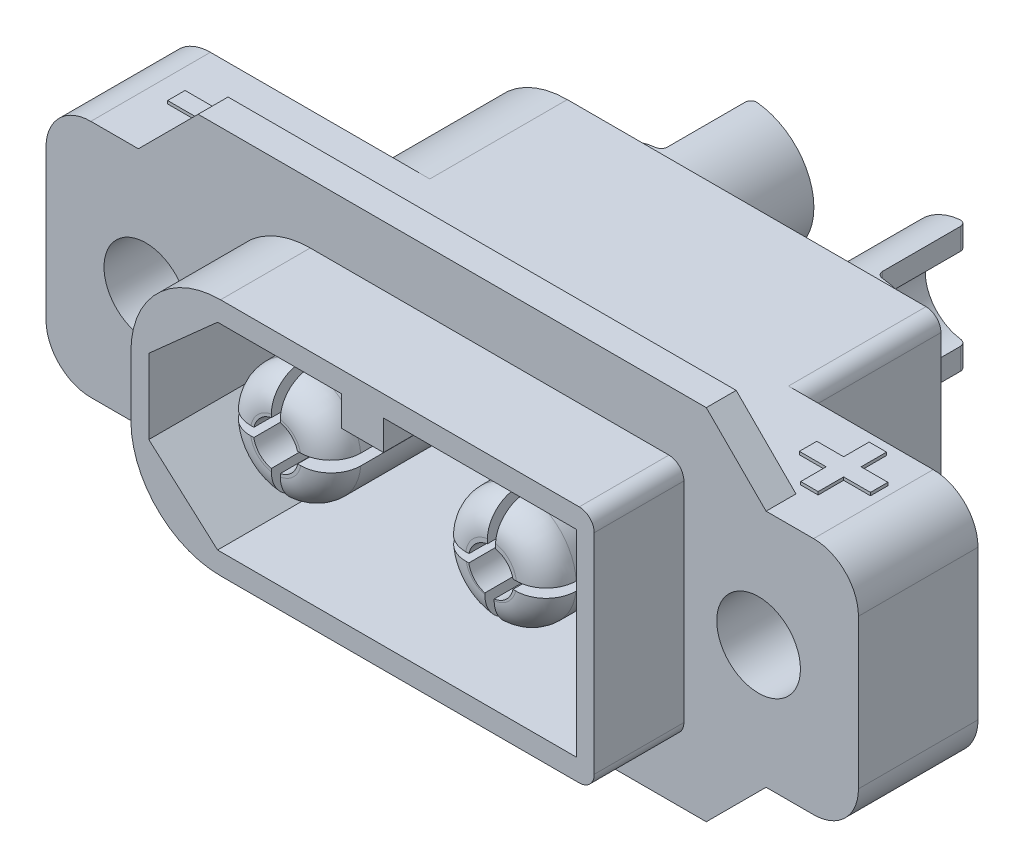
SolidWorks part; units mm, degrees
ref_plane "Front Plane" through (0, 0, 0) normal (0, 0, 1) x (1, 0, 0)
ref_plane "Top Plane" through (0, 0, 0) normal (0, 1, 0) x (1, 0, 0)
ref_plane "Right Plane" through (0, 0, 0) normal (1, 0, 0) x (0, 0, -1)
sketch "Sketch1" plane through (0, 0, 0) normal (0, 0, 1) x (1, 0, 0)
  line L1 (7.75, -4) -> (-7.75, -4)
  line L2 (7.75, -4) -> (7.75, 4)
  line L3 (7.75, 4) -> (-7.75, 4)
  line L4 (-7.75, -4) -> (-7.75, 4)
  line L5 (7.75, -4) -> (-7.75, 4) construction
  line L6 (7.75, 4) -> (-7.75, -4) construction
  point P0 (0, 0)
  dimension "D1" = 15.5
  dimension "D2" = 8
extrude "Boss-Extrude1" add sketch "Sketch1" against normal blind 8.6 and the other way blind 3
fillet "Fillet1" radius 3 2 edges at (-7.75, -4, -2.8) (-7.75, 4, -2.8)
fillet "Fillet2" radius 0.5 2 edges at (7.75, -4, -2.8) (7.75, 4, -2.8)
sketch "Sketch2" plane through (0, 0, 0) normal (0, 0, 1) x (1, 0, 0)
  line L0 (7.25, 4) -> (-4.75, 4) construction
  line L1 (13.59, -4) -> (-13.59, -4)
  line L2 (13.59, -4) -> (13.59, 4)
  line L3 (13.59, 4) -> (-13.59, 4)
  line L4 (-13.59, -4) -> (-13.59, 4)
  line L5 (13.59, -4) -> (-13.59, 4) construction
  line L6 (13.59, 4) -> (-13.59, -4) construction
  point P0 (0, 0)
  dimension "D1" = 0
  dimension "D2" = 27.18
extrude "Boss-Extrude2" add sketch "Sketch2" against normal blind 4
fillet "Fillet3" radius 1.5 4 edges at (-13.59, -4, -2) (13.59, -4, -2) (13.59, 4, -2) (-13.59, 4, -2)
sketch "Sketch3" plane through (0, 0, -8.6) normal (0, 0, -1) x (-1, 0, 0)
  line L8 (-7.05, 3.3) -> (-7.05, -3.3)
  line L9 (-7.05, -3.3) -> (4.75, -3.3)
  line L10 (7.05, -1) -> (7.05, 1)
  line L11 (4.75, 3.3) -> (-7.05, 3.3)
  line L12 (-7.05, 3.3) -> (-7.05, -3.3)
  line L13 (-7.05, -3.3) -> (4.75, -3.3)
  line L14 (7.05, -1) -> (7.05, 1)
  line L15 (4.75, 3.3) -> (-7.05, 3.3)
  arc A8 (4.75, -3.3) -> (7.05, -1) centre (4.75, -1) ccw
  arc A9 (7.05, 1) -> (4.75, 3.3) centre (4.75, 1) ccw
  arc A10 (4.75, -3.3) -> (7.05, -1) centre (4.75, -1) ccw
  arc A11 (7.05, 1) -> (4.75, 3.3) centre (4.75, 1) ccw
  dimension "D1" = 0.7
extrude "Cut-Extrude1" cut sketch "Sketch3" against normal blind 1
sketch "Sketch4" plane through (0, 0, 0) normal (0, 0, 1) x (1, 0, 0)
  line L0 (8.5, 6) -> (10.5, 4)
  line L1 (8.5, -6) -> (-8.5, -6)
  line L3 (8.5, 6) -> (-8.5, 6)
  line L5 (8.5, -6) -> (-8.5, 6) construction
  line L6 (8.5, 6) -> (-8.5, -6) construction
  line L7 (12.09, 4) -> (7.25, 4) construction
  line L8 (10.5, 4) -> (10.5, -4)
  line L9 (7.25, -4) -> (12.09, -4) construction
  line L10 (10.5, -4) -> (8.5, -6)
  line L11 (-8.5, -6) -> (-10.5, -4)
  line L12 (-12.09, -4) -> (-4.75, -4) construction
  line L13 (-10.5, -4) -> (-10.5, 4)
  line L14 (-4.75, 4) -> (-12.09, 4) construction
  line L15 (-10.5, 4) -> (-8.5, 6)
  point P0 (0, 0)
  dimension "D1" = 17
  dimension "D2" = 12
extrude "Boss-Extrude3" add sketch "Sketch4" against normal blind 1
sketch "Sketch5" plane through (0, 0, 0) normal (0, 0, 1) x (1, 0, 0)
  circle A0 centre (10.25, 0) radius 1.4
  circle A1 centre (-10.25, 0) radius 1.4
  dimension "D1" = 2.8
  dimension "D2" = 2.8
  dimension "D3" = 20.5
  dimension "D4" = 10.25
extrude "Cut-Extrude2" cut sketch "Sketch5" against normal through all
sketch "Sketch6" plane through (0, 0, -4) normal (0, 0, -1) x (-1, 0, 0)
  line L0 (13.59, 2.5) -> (13.59, -2.5) construction
  line L1 (-10.25, 2.8175) -> (-12.69, 1.4087)
  line L2 (-12.69, 1.4087) -> (-12.69, -1.4087)
  line L3 (-12.69, -1.4087) -> (-10.25, -2.8175)
  line L4 (-10.25, -2.8175) -> (-7.81, -1.4087)
  line L5 (-7.81, -1.4087) -> (-7.81, 1.4087)
  line L6 (-7.81, 1.4087) -> (-10.25, 2.8175)
  line L7 (10.25, 2.8175) -> (7.81, 1.4087)
  line L8 (7.81, 1.4087) -> (7.81, -1.4087)
  line L9 (7.81, -1.4087) -> (10.25, -2.8175)
  line L10 (10.25, -2.8175) -> (12.69, -1.4087)
  line L11 (12.69, -1.4087) -> (12.69, 1.4087)
  line L12 (12.69, 1.4087) -> (10.25, 2.8175)
  line L13 (-13.59, -2.5) -> (-13.59, 2.5) construction
  circle A0 centre (-10.25, 0) radius 2.44 construction
  circle A1 centre (10.25, 0) radius 2.44 construction
  dimension "D1" = 4.88
  dimension "D2" = 4.88
extrude "Cut-Extrude3" cut sketch "Sketch6" against normal blind 2
sketch "Sketch7" plane through (0, 0, 3) normal (0, 0, 1) x (1, 0, 0)
  line L0 (7.15, 3.3) -> (7.15, -3.3)
  line L1 (7.15, -3.3) -> (-4.85, -3.3)
  line L2 (-4.85, -3.3) -> (-7.15, -1.25)
  line L3 (-7.15, -1.25) -> (-7.15, 1.25)
  line L4 (-7.15, 1.25) -> (-4.85, 3.3)
  line L5 (-4.85, 3.3) -> (-0.7, 3.3)
  line L6 (0.7, 3.3) -> (7.15, 3.3)
  line L8 (-0.7, 3.3) -> (-0.7, 2.3)
  line L9 (-0.7, 2.3) -> (0.7, 2.3)
  line L10 (0.7, 3.3) -> (0.7, 2.3)
  line L11 (0, 3.3) -> (0.7, 2.3) construction
  line L12 (-0.7, 2.3) -> (0, 3.3) construction
  point P2 (0, 3.3)
  dimension "D1" = 6.6
  dimension "D2" = 3.3
  dimension "D3" = 14.3
  dimension "D4" = 7.15
  dimension "D5" = 12
  dimension "D6" = 12
  dimension "D7" = 2.5
  dimension "D8" = 1.25
  dimension "D9" = 1.4
  dimension "D10" = 5.6
extrude "Cut-Extrude4" cut sketch "Sketch7" against normal blind 8.8
sketch "Sketch8" plane through (0, 0, -7.6) normal (0, 0, -1) x (-1, 0, 0)
  circle A0 centre (-3.6, 0) radius 2.1
  circle A1 centre (3.6, 0) radius 2.1
  dimension "D1" = 4.2
  dimension "D2" = 4.2
  dimension "D3" = 7.2
  dimension "D4" = 3.6
extrude "Boss-Extrude4" add sketch "Sketch8" along normal blind 6
hole_wizard "Ø2.5mm Dowel Hole1" positions "Sketch9" profile "Sketch10" hole size "Ø2.5" standard "DIN"
sketch "Sketch9" plane through (0, 0, -13.6) normal (0, 0, -1) x (-1, 0, 0)
  point P0 (-3.6, 0)
  point P3 (3.6, 0)
sketch "Sketch10" plane through (3.6, 0, -13.6) normal (1, 0, 0) x (0, 1, 0)
  line L0 (0, 0) -> (0, 6.8262)
  line L1 (0, 6.8262) -> (1.375, 6)
  line L2 (1.375, 6) -> (1.375, 0)
  line L5 (1.375, 0) -> (0, 0)
  line L10 (0, 6.8262) -> (-1.375, 6) construction
  line L11 (0, -6.35) -> (0, 107.95) construction
  dimension "Hole Dia." = 2.75
  dimension "Hole Depth" = 6
  dimension "Drill Angle" = 118
sketch "Sketch11" plane through (0, 0, 0) normal (0, 1, 0) x (1, 0, 0)
  line L0 (1.5, 13.6) -> (1.5, 7.6) construction
  line L1 (-3.6, 10.6) -> (-7.0404, 10.6)
  line L2 (-3.6, 10.6) -> (-3.6, 15.392)
  line L3 (-3.6, 15.392) -> (-7.0404, 15.392)
  line L4 (-7.0404, 10.6) -> (-7.0404, 15.392)
  line L5 (3.6, 10.6) -> (6.9913, 10.6)
  line L6 (3.6, 10.6) -> (3.6, 15.1421)
  line L7 (3.6, 15.1421) -> (6.9913, 15.1421)
  line L8 (6.9913, 10.6) -> (6.9913, 15.1421)
  line L9 (-5.7, 13.6) -> (-5.7, 7.6) construction
  line L10 (-1.5, 13.6) -> (-5.7, 13.6) construction
  line L11 (5.7, 13.6) -> (1.5, 13.6) construction
  dimension "D1" = 2.1
  dimension "D2" = 2.1
  dimension "D3" = 3
  dimension "D4" = 3
extrude "Cut-Extrude5" cut sketch "Sketch11" against normal mid plane 8.8
fillet "Fillet4" radius 0.2 8 edges at (3.6, -1.7375, -13.6) (3.6, 1.7375, -13.6) (-3.6, 1.7375, -13.6) (-3.6, -1.7375, -13.6) (3.6, -1.7375, -10.6) (3.6, 1.7375, -10.6) (-3.6, 1.7375, -10.6) (-3.6, -1.7375, -10.6)
sketch "Sketch12" plane through (0, 0, -5.8) normal (0, 0, 1) x (1, 0, 0)
  circle A0 centre (-3.6, 0) radius 1.85
  circle A1 centre (3.6, 0) radius 1.85
  dimension "D1" = 3.7
  dimension "D2" = 3.7
  dimension "D3" = 7.2
  dimension "D4" = 3.6
extrude "Boss-Extrude5" add sketch "Sketch12" along normal blind 8.1
fillet "Fillet5" radius 1 2 edges at (-1.75, 0, 2.3) (5.45, 0, 2.3)
sketch "Sketch14" plane through (0, 0, 2.3) normal (0, 0, 1) x (1, 0, 0)
  line L0 (-3.75, 0.7348) -> (-3.75, 2.5189)
  line L1 (-3.75, -2.5189) -> (-3.45, -2.5189)
  line L2 (-3.75, -2.5189) -> (-3.75, -0.7348)
  line L3 (-3.75, 2.5189) -> (-3.45, 2.5189)
  line L4 (-3.45, -2.5189) -> (-3.45, -0.7348)
  line L5 (-3.75, -2.5189) -> (-3.45, 2.5189) construction
  line L6 (-3.75, 2.5189) -> (-3.45, -2.5189) construction
  line L7 (-0.8121, 0.2003) -> (-2.8773, 0.2003)
  line L8 (-0.8121, 0.2003) -> (-0.8121, -0.1649)
  line L9 (-0.8121, -0.1649) -> (-2.8683, -0.1649)
  line L10 (-5.8901, 0.1354) -> (-5.8901, -0.1646)
  line L11 (-0.8121, 0.2003) -> (-5.8901, -0.1646) construction
  line L12 (-0.8121, -0.1649) -> (-5.8901, 0.1354) construction
  line L13 (3.3921, -2.6186) -> (3.704, -2.6186)
  line L14 (3.3921, -2.6186) -> (3.3921, -0.7716)
  line L15 (3.5, 2.5189) -> (3.8, 2.5189)
  line L16 (3.704, -2.6186) -> (3.704, -0.7921)
  line L17 (3.3921, -2.6186) -> (3.8, 2.5189) construction
  line L18 (3.5, 2.5189) -> (3.704, -2.6186) construction
  line L19 (6.0204, 0.1) -> (4.3309, 0.1)
  line L20 (6.0204, 0.1) -> (6.0204, -0.1995)
  line L21 (6.0204, -0.1995) -> (4.331, -0.1995)
  line L22 (1.1796, 0.1) -> (1.1796, -0.2)
  line L23 (6.0204, 0.1) -> (1.1796, -0.2) construction
  line L24 (6.0204, -0.1995) -> (1.1796, 0.1) construction
  line L25 (-4.3317, 0.1645) -> (-5.8901, 0.1354)
  line L26 (-3.45, 0.7348) -> (-3.45, 2.5189)
  line L28 (-4.3377, -0.1354) -> (-5.8901, -0.1646)
  line L30 (2.8558, -0.1707) -> (1.1796, -0.2)
  line L32 (3.4752, 0.6903) -> (3.5, 2.5189)
  line L33 (2.8612, 0.1) -> (1.1796, 0.1)
  line L35 (3.746, 0.685) -> (3.8, 2.5189)
  arc A0 (-3.75, 0.7348) -> (-4.3317, 0.1645) centre (-3.6, 0) ccw
  arc A1 (3.4752, 0.6903) -> (2.8612, 0.1) centre (3.596, -0.0499) ccw
  arc A2 (-4.3377, -0.1354) -> (-3.75, -0.7348) centre (-3.6, 0) ccw
  arc A3 (-3.45, -0.7348) -> (-2.8683, -0.1649) centre (-3.6, 0) ccw
  arc A4 (-2.8773, 0.2003) -> (-3.45, 0.7348) centre (-3.6, 0) ccw
  arc A5 (2.8558, -0.1707) -> (3.3921, -0.7716) centre (3.596, -0.0499) ccw
  arc A6 (4.3309, 0.1) -> (3.746, 0.685) centre (3.596, -0.0499) ccw
  arc A7 (3.704, -0.7921) -> (4.331, -0.1995) centre (3.596, -0.0499) ccw
  point P0 (-3.6, 0)
  point P6 (-3.6, 0)
  point P11 (3.6, 0)
  point P17 (3.602, -0.0499)
  dimension "D5" = 1.5
  dimension "D6" = 1.5
  dimension "D1" = 0.3
  dimension "D2" = 0.3
  dimension "D3" = 0.3
  dimension "D4" = 0.3
extrude "Cut-Extrude6" cut sketch "Sketch14" against normal up to surface (8.1 mm away) up to face at (1.75, 0, -5.8)
sketch "Sketch15" plane through (0, 4, 0) normal (0, 1, 0) x (1, 0, 0)
  line L0 (-12, 0.8) -> (12, 0.8) construction
  text T0 "<b>-              +</b>"
  dimension "D1" = 24
  dimension "D2" = 12
  dimension "D3" = 0.8
extrude "Boss-Extrude6" add sketch "Sketch15" along normal blind 0.1
